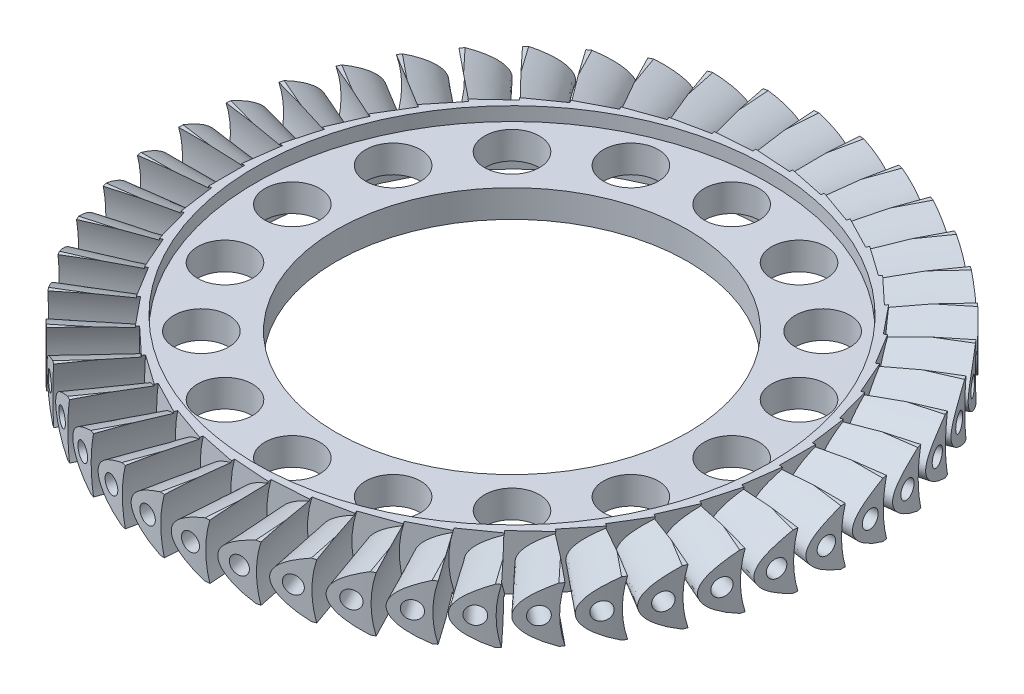
SolidWorks part; units mm, degrees
material "AISI 316 Stainless Steel Sheet (SS)"
ref_plane "Front Plane" through (0, 0, 0) normal (0, 0, 1) x (1, 0, 0)
ref_plane "Top Plane" through (0, 0, 0) normal (0, 1, 0) x (1, 0, 0)
ref_plane "Right Plane" through (0, 0, 0) normal (1, 0, 0) x (0, 0, -1)
ref_axis "Axis1" through (0, 11.1262, 0) along (0, -1, 0)
sketch "Sketch3" plane through (0, 0, 0) normal (0, 0, 1) x (1, 0, 0)
  line L1 (40.64, -3.175) -> (59.3725, -3.175)
  line L2 (59.3725, -3.175) -> (59.3725, -6.35)
  line L3 (59.3725, -6.35) -> (76.2, -6.35)
  line L4 (76.2, -6.35) -> (76.2, 6.35)
  line L5 (76.2, 6.35) -> (59.3725, 6.35)
  line L6 (59.3725, 6.35) -> (59.3725, 3.175)
  line L7 (59.3725, 3.175) -> (40.64, 3.175)
  line L8 (60.96, 6.35) -> (60.96, -6.35) construction
  line L9 (40.64, -3.175) -> (40.64, 3.175)
  line L10 (0, -10.1148) -> (0, 10.1148) construction
  point P11 (0, 0)
  point P12 (40.64, 0)
  dimension "D1" = 40.64
  dimension "D2" = 60.96
  dimension "D3" = 6.35
  dimension "D4" = 12.7
  dimension "D5" = 1.5875
  dimension "D6" = 76.2
revolve "Revolve1" add sketch "Sketch3" angle 360 about L10
ref_plane "Plane1" through (76.2, 0, 0) normal (1, 0, 0) x (0, 0, -1)
sketch "Sketch2" plane through (76.2, 0, 0) normal (1, 0, 0) x (0, 0, -1)
  line L0 (0.8868, 6.35) -> (2.3701, 11.5572) construction
  line L1 (0.8868, -6.35) -> (0.8868, 6.35) construction
  line L2 (0.8868, 6.35) -> (10.2542, 6.35)
  line L3 (0.8868, -6.35) -> (10.2542, -6.35)
  line L4 (-6.802, 0) -> (0, 0) construction
  arc A0 (0.8868, 6.35) -> (0.8868, -6.35) centre (23.1786, 0) ccw
  circle A1 centre (-3.401, 0) radius 2.032
  ellipse E0 centre (43.998, 0) end of major axis (94.798, 0) minor radius 12.0047 (0.8868, -6.35) -> (0.8868, 6.35) cw construction
  ellipse E1 centre (53.3654, 0) end of major axis (104.1654, 0) minor radius 12.0047 (10.2542, -6.35) -> (10.2542, 6.35) cw
  point P5 (0, 0)
  point P22 (-3.401, 0)
  dimension "D7" = 4.064
  dimension "D1" = 15.9
  dimension "D2" = 12.7
  dimension "D3" = 2.5654
  dimension "D5" = 9.3674
  dimension "D6" = 50.8
  dimension "D4" = 2
extrude "Cut-Extrude1" cut sketch "Sketch2" against normal up to vertex (15.24 mm away) up to point (60.96, 6.35, 0)
pattern_circular "CirPattern1" count 46 over 360 about axis through (0, -10.1148, 0) along (0, -1, 0) of "Cut-Extrude1" reverse direction yes
sketch "Sketch4" plane through (0, 3.175, 0) normal (0, 1, 0) x (1, 0, 0)
  line L0 (0, 0) -> (50.8, 0) construction
  circle A0 centre (50.8, 0) radius 6.35
  dimension "D2" = 12.7
  dimension "D1" = 50.8
extrude "Cut-Extrude2" cut sketch "Sketch4" against normal through all
pattern_circular "CirPattern2" count 16 over 360 about axis through (0, 11.1262, 0) along (0, -1, 0) of "Cut-Extrude2"
equation "\"D2@Sketch2\"=\"blade width@[TP] [Turb] Turbine.Assembly\""
equation "\"D3@Sketch2\"=\"blade opening@[TP] [Turb] Turbine.Assembly\""
equation "\"D5@Sketch2\"=2*pi*\"rotor pitchline@[TP] [Turb] Turbine.Assembly\"/\"blade number@[TP] [Turb] Turbine.Assembly\""
equation "\"D1@Sketch2\"=\"blade angle@[TP] [Turb] Turbine.Assembly\""
